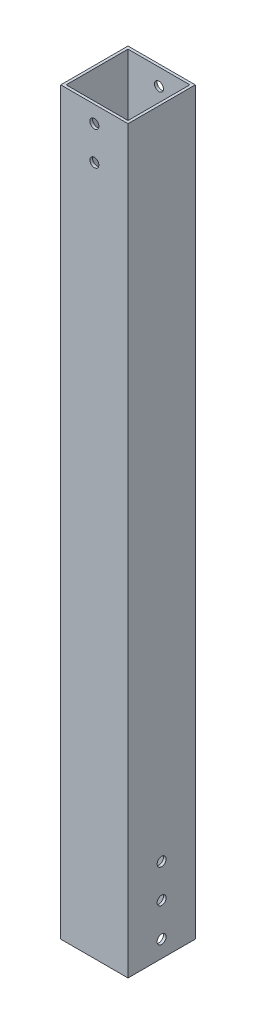
SolidWorks part; units mm, degrees
material "6061 Alloy"
ref_plane "Front Plane" through (0, 0, 0) normal (0, 0, 1) x (1, 0, 0)
ref_plane "Top Plane" through (0, 0, 0) normal (0, 1, 0) x (1, 0, 0)
ref_plane "Right Plane" through (0, 0, 0) normal (1, 0, 0) x (0, 0, -1)
sketch "Sketch1" plane through (0, 0, 0) normal (0, 1, 0) x (1, 0, 0)
  line L1 (19.05, 19.05) -> (-19.05, 19.05)
  line L2 (19.05, 19.05) -> (19.05, -19.05)
  line L3 (19.05, -19.05) -> (-19.05, -19.05)
  line L4 (-19.05, 19.05) -> (-19.05, -19.05)
  line L5 (19.05, 19.05) -> (-19.05, -19.05) construction
  line L6 (19.05, -19.05) -> (-19.05, 19.05) construction
  point P0 (0, 0)
  dimension "D1" = 38.1
extrude "Extrude-Thin1" add sketch "Sketch1" along normal blind 419.1 thin thin type one direction reverse wall 1.524
sketch "Sketch2" plane through (19.05, 0, 0) normal (1, 0, 0) x (0, 0, -1)
  line L0 (-19.05, 0) -> (19.05, 0) construction
  circle A0 centre (0, 9.525) radius 2.54
  circle A1 centre (0, 28.575) radius 2.54
  circle A2 centre (0, 47.625) radius 2.54
  dimension "D1" = 5.08
  dimension "D4" = 19.05
  dimension "D2" = 9.525
  dimension "D3" = 28.575
hole_wizard "#10 Clearance Hole1" positions "Sketch3" profile "Sketch4" hole size "#10" standard "ANSI Inch" end condition through all
sketch "Sketch3" plane through (19.05, 0, 0) normal (1, 0, 0) x (0, 0, -1)
  point P0 (0, 9.525)
  point P3 (0, 28.575)
  point P6 (0, 47.625)
sketch "Sketch4" plane through (19.05, 9.525, 0) normal (0, 1, 0) x (0, 0, -1)
  line L0 (0, 0) -> (0, 38.1)
  line L1 (0, 38.1) -> (2.5527, 38.1)
  line L2 (2.5527, 38.1) -> (2.5527, 0)
  line L5 (2.5527, 0) -> (0, 0)
  line L11 (0, -6.35) -> (0, 107.95) construction
  dimension "Thru Hole Dia." = 5.1054
  dimension "Thru Hole Depth" = 38.1
sketch "Sketch5" plane through (0, 0, 19.05) normal (0, 0, 1) x (1, 0, 0)
  line L0 (-19.05, 419.1) -> (19.05, 419.1) construction
  circle A0 centre (0, 409.575) radius 2.54
  circle A1 centre (0, 390.525) radius 2.54
  dimension "D1" = 5.08
  dimension "D2" = 9.525
  dimension "D3" = 28.575
hole_wizard "#10 Clearance Hole2" positions "Sketch6" profile "Sketch7" hole size "#10" standard "ANSI Inch" end condition through all
sketch "Sketch6" plane through (0, 0, 19.05) normal (0, 0, 1) x (1, 0, 0)
  point P0 (0, 390.525)
  point P3 (0, 409.575)
sketch "Sketch7" plane through (0, 390.525, 19.05) normal (1, 0, 0) x (0, -1, 0)
  line L0 (0, 0) -> (0, 38.1)
  line L1 (0, 38.1) -> (2.5527, 38.1)
  line L2 (2.5527, 38.1) -> (2.5527, 0)
  line L5 (2.5527, 0) -> (0, 0)
  line L11 (0, -6.35) -> (0, 107.95) construction
  dimension "Thru Hole Dia." = 5.1054
  dimension "Thru Hole Depth" = 38.1
sketch "Sketch8" plane through (19.05, 0, 0) normal (1, 0, 0) x (0, 0, -1)
  line L0 (-19.05, 59.7027) -> (19.05, 59.7027) construction
  line L1 (-19.05, 419.1) -> (-19.05, 0) construction
  line L2 (19.05, 419.1) -> (19.05, 0) construction
  line L3 (17.526, 419.1) -> (-17.526, 419.1) construction
  line L4 (-7.7094, 379.4285) -> (6.35, 379.4285) construction
  line L5 (-3.175, 379.4285) -> (3.175, 379.4285)
  line L6 (6.35, 376.2535) -> (6.35, 358.807)
  line L7 (0.1915, 357.7211) -> (-6.1585, 375.1676)
  line L8 (-3.175, 382.6035) -> (3.175, 382.6035)
  line L9 (-6.35, 385.7785) -> (-6.35, 403.225)
  line L10 (-0.1915, 404.3109) -> (6.1585, 386.8644)
  line L11 (-0.1915, 352.7934) -> (6.1585, 335.347)
  line L12 (-6.35, 419.1) -> (-6.35, 0) construction
  line L13 (-19.05, 419.1) -> (19.05, 419.1) construction
  line L14 (-19.05, 0) -> (19.05, 0) construction
  line L15 (6.35, 0) -> (6.35, 419.1) construction
  line L16 (-19.05, 348.6497) -> (-6.35, 348.6497) construction
  line L17 (6.35, 348.6497) -> (19.05, 348.6497) construction
  line L18 (-6.35, 334.261) -> (-6.35, 351.7075)
  line L19 (-3.175, 331.086) -> (3.175, 331.086)
  line L20 (-3.175, 327.911) -> (3.175, 327.911)
  line L21 (0.1915, 306.2036) -> (-6.1585, 323.6501)
  line L22 (6.35, 324.736) -> (6.35, 307.2896)
  line L23 (-0.1915, 301.276) -> (6.1585, 283.8295)
  line L24 (-6.35, 282.7436) -> (-6.35, 300.19)
  line L25 (-3.175, 279.5686) -> (3.175, 279.5686)
  line L26 (-3.175, 276.3936) -> (3.175, 276.3936)
  line L27 (0.1915, 254.6862) -> (-6.1585, 272.1326)
  line L28 (6.35, 273.2186) -> (6.35, 255.7721)
  line L29 (-0.1915, 249.7585) -> (6.1585, 232.312)
  line L30 (-6.35, 231.2261) -> (-6.35, 248.6726)
  line L31 (-3.175, 228.0511) -> (3.175, 228.0511)
  line L32 (-3.175, 224.8761) -> (3.175, 224.8761)
  line L33 (0.1915, 203.1687) -> (-6.1585, 220.6152)
  line L34 (6.35, 221.7011) -> (6.35, 204.2546)
  line L35 (-0.1915, 198.241) -> (6.1585, 180.7945)
  line L36 (-6.35, 179.7086) -> (-6.35, 197.1551)
  line L37 (-3.175, 176.5336) -> (3.175, 176.5336)
  line L38 (-3.175, 173.3586) -> (3.175, 173.3586)
  line L39 (0.1915, 151.6512) -> (-6.1585, 169.0977)
  line L40 (6.35, 170.1836) -> (6.35, 152.7371)
  line L41 (-0.1915, 146.7235) -> (6.1585, 129.277)
  line L42 (-6.35, 128.1911) -> (-6.35, 145.6376)
  line L43 (-3.175, 125.0161) -> (3.175, 125.0161)
  line L47 (6.35, 118.6661) -> (6.35, 101.2196) [skipped]
  line L48 (0.1915, 100.1337) -> (-6.1585, 117.5802) [skipped]
  line L49 (-3.175, 121.8411) -> (3.175, 121.8411) [skipped]
  circle A0 centre (0, 47.625) radius 2.5527 construction
  arc A1 (-6.1585, 375.1676) -> (-3.175, 379.4285) centre (-3.175, 376.2535) cw
  arc A2 (3.175, 379.4285) -> (6.35, 376.2535) centre (3.175, 376.2535) cw
  arc A3 (6.35, 358.807) -> (0.1915, 357.7211) centre (3.175, 358.807) cw
  arc A4 (6.1585, 386.8644) -> (3.175, 382.6035) centre (3.175, 385.7785) cw
  arc A5 (-6.35, 403.225) -> (-0.1915, 404.3109) centre (-3.175, 403.225) cw
  arc A6 (-6.35, 385.7785) -> (-3.175, 382.6035) centre (-3.175, 385.7785) ccw
  arc A7 (-6.35, 351.7075) -> (-0.1915, 352.7934) centre (-3.175, 351.7075) cw
  arc A8 (-6.35, 334.261) -> (-3.175, 331.086) centre (-3.175, 334.261) ccw
  arc A9 (6.1585, 335.347) -> (3.175, 331.086) centre (3.175, 334.261) cw
  arc A10 (-6.1585, 323.6501) -> (-3.175, 327.911) centre (-3.175, 324.736) cw
  arc A11 (6.35, 307.2896) -> (0.1915, 306.2036) centre (3.175, 307.2896) cw
  arc A12 (3.175, 327.911) -> (6.35, 324.736) centre (3.175, 324.736) cw
  arc A13 (-6.35, 300.19) -> (-0.1915, 301.276) centre (-3.175, 300.19) cw
  arc A14 (-6.35, 282.7436) -> (-3.175, 279.5686) centre (-3.175, 282.7436) ccw
  arc A15 (6.1585, 283.8295) -> (3.175, 279.5686) centre (3.175, 282.7436) cw
  arc A16 (-6.1585, 272.1326) -> (-3.175, 276.3936) centre (-3.175, 273.2186) cw
  arc A17 (6.35, 255.7721) -> (0.1915, 254.6862) centre (3.175, 255.7721) cw
  arc A18 (3.175, 276.3936) -> (6.35, 273.2186) centre (3.175, 273.2186) cw
  arc A19 (-6.35, 248.6726) -> (-0.1915, 249.7585) centre (-3.175, 248.6726) cw
  arc A20 (-6.35, 231.2261) -> (-3.175, 228.0511) centre (-3.175, 231.2261) ccw
  arc A21 (6.1585, 232.312) -> (3.175, 228.0511) centre (3.175, 231.2261) cw
  arc A22 (-6.1585, 220.6152) -> (-3.175, 224.8761) centre (-3.175, 221.7011) cw
  arc A23 (6.35, 204.2546) -> (0.1915, 203.1687) centre (3.175, 204.2546) cw
  arc A24 (3.175, 224.8761) -> (6.35, 221.7011) centre (3.175, 221.7011) cw
  arc A25 (-6.35, 197.1551) -> (-0.1915, 198.241) centre (-3.175, 197.1551) cw
  arc A26 (-6.35, 179.7086) -> (-3.175, 176.5336) centre (-3.175, 179.7086) ccw
  arc A27 (6.1585, 180.7945) -> (3.175, 176.5336) centre (3.175, 179.7086) cw
  arc A28 (-6.1585, 169.0977) -> (-3.175, 173.3586) centre (-3.175, 170.1836) cw
  arc A29 (6.35, 152.7371) -> (0.1915, 151.6512) centre (3.175, 152.7371) cw
  arc A30 (3.175, 173.3586) -> (6.35, 170.1836) centre (3.175, 170.1836) cw
  arc A31 (-6.35, 145.6376) -> (-0.1915, 146.7235) centre (-3.175, 145.6376) cw
  arc A32 (-6.35, 128.1911) -> (-3.175, 125.0161) centre (-3.175, 128.1911) ccw
  arc A33 (6.1585, 129.277) -> (3.175, 125.0161) centre (3.175, 128.1911) cw
  arc A37 (6.35, 101.2196) -> (0.1915, 100.1337) centre (3.175, 101.2196) cw [skipped]
  arc A38 (3.175, 121.8411) -> (6.35, 118.6661) centre (3.175, 118.6661) cw [skipped]
  arc A39 (-6.1585, 117.5802) -> (-3.175, 121.8411) centre (-3.175, 118.6661) cw [skipped]
  dimension "D1" = 9.525
  dimension "D3" = 3.175
  dimension "D5" = 15.875
  dimension "D8" = 3.175
  dimension "D2" = 20
  dimension "D4" = 12.7
  dimension "D6" = 3.175
  dimension "D7" = 6
extrude "Cut-Extrude1" [suppressed] cut sketch "Sketch8" against normal through all
sketch "Sketch9" plane through (0, 0, 19.05) normal (0, 0, 1) x (1, 0, 0)
  line L0 (-7.7094, 381) -> (6.35, 381) construction
  line L1 (-3.175, 381) -> (3.175, 381)
  line L2 (6.35, 377.825) -> (6.35, 360.3785)
  line L3 (0.1915, 359.2926) -> (-6.1585, 376.7391)
  line L4 (-3.175, 332.6575) -> (3.175, 332.6575)
  line L5 (-6.35, 335.8325) -> (-6.35, 353.279)
  line L6 (-0.1915, 354.3649) -> (6.1585, 336.9184)
  line L7 (-3.175, 329.4825) -> (3.175, 329.4825)
  line L8 (-6.35, 419.1) -> (-6.35, 0) construction
  line L9 (-19.05, 419.1) -> (19.05, 419.1) construction
  line L10 (-19.05, 0) -> (19.05, 0) construction
  line L11 (6.35, 0) -> (6.35, 419.1) construction
  line L12 (-19.05, 360.2771) -> (-6.35, 360.2771) construction
  line L13 (-19.05, 419.1) -> (-19.05, 0) construction
  line L14 (6.35, 360.2771) -> (19.05, 360.2771) construction
  line L15 (19.05, 419.1) -> (19.05, 0) construction
  line L16 (0.1915, 307.7751) -> (-6.1585, 325.2216)
  line L17 (6.35, 326.3075) -> (6.35, 308.861)
  line L18 (-6.35, 284.315) -> (-6.35, 301.7615)
  line L19 (-0.1915, 302.8474) -> (6.1585, 285.401)
  line L20 (-3.175, 281.14) -> (3.175, 281.14)
  line L21 (-3.175, 277.965) -> (3.175, 277.965)
  line L22 (0.1915, 256.2576) -> (-6.1585, 273.7041)
  line L23 (6.35, 274.79) -> (6.35, 257.3436)
  line L24 (-6.35, 232.7976) -> (-6.35, 250.244)
  line L25 (-0.1915, 251.33) -> (6.1585, 233.8835)
  line L26 (-3.175, 229.6226) -> (3.175, 229.6226)
  line L27 (-3.175, 226.4476) -> (3.175, 226.4476)
  line L28 (0.1915, 204.7402) -> (-6.1585, 222.1866)
  line L29 (6.35, 223.2726) -> (6.35, 205.8261)
  line L30 (-6.35, 181.2801) -> (-6.35, 198.7266)
  line L31 (-0.1915, 199.8125) -> (6.1585, 182.366)
  line L32 (-3.175, 178.1051) -> (3.175, 178.1051)
  line L33 (-3.175, 174.9301) -> (3.175, 174.9301)
  line L34 (0.1915, 153.2227) -> (-6.1585, 170.6692)
  line L35 (6.35, 171.7551) -> (6.35, 154.3086)
  line L36 (-6.35, 129.7626) -> (-6.35, 147.2091)
  line L37 (-0.1915, 148.295) -> (6.1585, 130.8485)
  line L38 (-3.175, 126.5876) -> (3.175, 126.5876)
  line L39 (-3.175, 123.4126) -> (3.175, 123.4126)
  line L40 (0.1915, 101.7052) -> (-6.1585, 119.1517)
  line L41 (6.35, 120.2376) -> (6.35, 102.7911)
  line L42 (-6.35, 78.2451) -> (-6.35, 95.6916)
  line L43 (-0.1915, 96.7775) -> (6.1585, 79.331)
  line L44 (-3.175, 75.0701) -> (3.175, 75.0701)
  arc A0 (-6.1585, 376.7391) -> (-3.175, 381) centre (-3.175, 377.825) cw
  arc A1 (3.175, 381) -> (6.35, 377.825) centre (3.175, 377.825) cw
  arc A2 (6.35, 360.3785) -> (0.1915, 359.2926) centre (3.175, 360.3785) cw
  arc A3 (6.1585, 336.9184) -> (3.175, 332.6575) centre (3.175, 335.8325) cw
  arc A4 (-6.35, 353.279) -> (-0.1915, 354.3649) centre (-3.175, 353.279) cw
  arc A5 (-6.35, 335.8325) -> (-3.175, 332.6575) centre (-3.175, 335.8325) ccw
  circle A6 centre (0, 390.525) radius 2.5527 construction
  arc A7 (-6.1585, 325.2216) -> (-3.175, 329.4825) centre (-3.175, 326.3075) cw
  arc A8 (3.175, 329.4825) -> (6.35, 326.3075) centre (3.175, 326.3075) cw
  arc A9 (6.35, 308.861) -> (0.1915, 307.7751) centre (3.175, 308.861) cw
  arc A10 (-6.35, 301.7615) -> (-0.1915, 302.8474) centre (-3.175, 301.7615) cw
  arc A11 (6.1585, 285.401) -> (3.175, 281.14) centre (3.175, 284.315) cw
  arc A12 (-6.35, 284.315) -> (-3.175, 281.14) centre (-3.175, 284.315) ccw
  arc A13 (-6.1585, 273.7041) -> (-3.175, 277.965) centre (-3.175, 274.79) cw
  arc A14 (3.175, 277.965) -> (6.35, 274.79) centre (3.175, 274.79) cw
  arc A15 (6.35, 257.3436) -> (0.1915, 256.2576) centre (3.175, 257.3436) cw
  arc A16 (-6.35, 250.244) -> (-0.1915, 251.33) centre (-3.175, 250.244) cw
  arc A17 (6.1585, 233.8835) -> (3.175, 229.6226) centre (3.175, 232.7976) cw
  arc A18 (-6.35, 232.7976) -> (-3.175, 229.6226) centre (-3.175, 232.7976) ccw
  arc A19 (-6.1585, 222.1866) -> (-3.175, 226.4476) centre (-3.175, 223.2726) cw
  arc A20 (3.175, 226.4476) -> (6.35, 223.2726) centre (3.175, 223.2726) cw
  arc A21 (6.35, 205.8261) -> (0.1915, 204.7402) centre (3.175, 205.8261) cw
  arc A22 (-6.35, 198.7266) -> (-0.1915, 199.8125) centre (-3.175, 198.7266) cw
  arc A23 (6.1585, 182.366) -> (3.175, 178.1051) centre (3.175, 181.2801) cw
  arc A24 (-6.35, 181.2801) -> (-3.175, 178.1051) centre (-3.175, 181.2801) ccw
  arc A25 (-6.1585, 170.6692) -> (-3.175, 174.9301) centre (-3.175, 171.7551) cw
  arc A26 (3.175, 174.9301) -> (6.35, 171.7551) centre (3.175, 171.7551) cw
  arc A27 (6.35, 154.3086) -> (0.1915, 153.2227) centre (3.175, 154.3086) cw
  arc A28 (-6.35, 147.2091) -> (-0.1915, 148.295) centre (-3.175, 147.2091) cw
  arc A29 (6.1585, 130.8485) -> (3.175, 126.5876) centre (3.175, 129.7626) cw
  arc A30 (-6.35, 129.7626) -> (-3.175, 126.5876) centre (-3.175, 129.7626) ccw
  arc A31 (-6.1585, 119.1517) -> (-3.175, 123.4126) centre (-3.175, 120.2376) cw
  arc A32 (3.175, 123.4126) -> (6.35, 120.2376) centre (3.175, 120.2376) cw
  arc A33 (6.35, 102.7911) -> (0.1915, 101.7052) centre (3.175, 102.7911) cw
  arc A34 (-6.35, 95.6916) -> (-0.1915, 96.7775) centre (-3.175, 95.6916) cw
  arc A35 (6.1585, 79.331) -> (3.175, 75.0701) centre (3.175, 78.2451) cw
  arc A36 (-6.35, 78.2451) -> (-3.175, 75.0701) centre (-3.175, 78.2451) ccw
  dimension "D2" = 3.175
  dimension "D4" = 3.175
  dimension "D1" = 20
  dimension "D3" = 12.7
  dimension "D5" = 9.525
  dimension "D7" = 3.175
  dimension "D6" = 6
extrude "Cut-Extrude2" [suppressed] cut sketch "Sketch9" against normal through all
